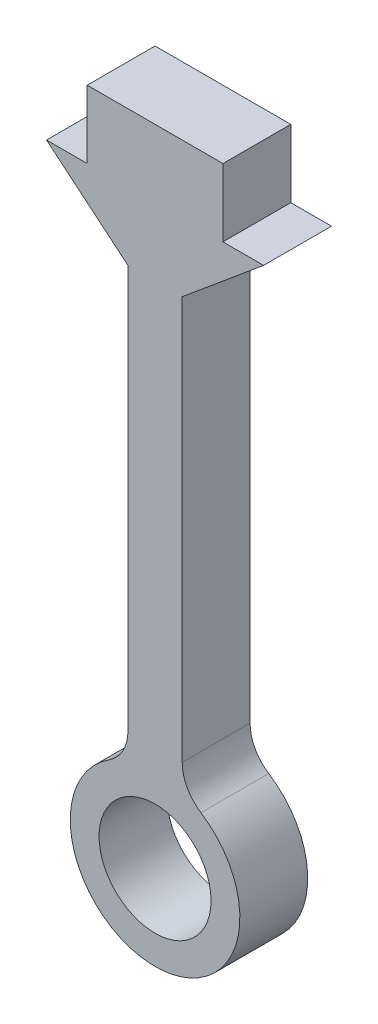
SolidWorks part; units mm, degrees
ref_plane "Plan de face" through (0, 0, 0) normal (0, 0, 1) x (1, 0, 0)
ref_plane "Plan de dessus" through (0, 0, 0) normal (0, 1, 0) x (1, 0, 0)
ref_plane "Plan de droite" through (0, 0, 0) normal (1, 0, 0) x (0, 0, -1)
sketch "Esquisse1" plane through (0, 0, 0) normal (0, 0, 1) x (1, 0, 0)
  line L1 (-2.8016, -1.3723) -> (-0.4016, -3.3723)
  line L2 (-0.4016, -3.3723) -> (1.1984, -3.3723)
  line L3 (1.1984, -3.3723) -> (3.5984, -1.3723)
  line L4 (0.3984, 0.6277) -> (0.3984, -1.3723) construction
  line L5 (-1.6016, -1.3723) -> (2.3984, -1.3723)
  line L6 (-1.6016, -1.3723) -> (-1.6016, 0.6277)
  line L7 (-1.6016, 0.6277) -> (2.3984, 0.6277)
  line L8 (2.3984, -1.3723) -> (2.3984, 0.6277)
  line L9 (-2.8016, -1.3723) -> (-1.6016, -1.3723)
  line L10 (-0.4016, -3.3723) -> (1.1984, -3.3723)
  line L11 (-0.4016, -3.3723) -> (-0.4016, -18.3723)
  line L12 (-0.4016, -18.3723) -> (1.1984, -18.3723)
  line L13 (1.1984, -3.3723) -> (1.1984, -18.3723)
  line L14 (2.3984, -1.3723) -> (3.5984, -1.3723)
  circle A0 centre (0.3984, -18.3723) radius 2.5
  circle A1 centre (0.3984, -18.3723) radius 1.65
  point P15 (0, 0)
  dimension "D7" = 3.3
  dimension "D8" = 5
  dimension "D1" = 2
  dimension "D2" = 1.6
  dimension "D3" = 1.2
  dimension "D4" = 4
  dimension "D5" = 2
  dimension "D6" = 15
extrude "Boss.-Extru.1" add sketch "Esquisse1" along normal blind 2 contours A0 L13 L2 L11 | L2 L3 L5 L1 | L7 L4 L5 L8 | L4 L7 L6 | A1 L13 A0 L11 | A1 L11 A0 L13 region at (0.3984, -2.1723, 0) region at (0.3984, -9.644, 0) region at (-0.6016, -0.3723, 0) region at (0.3984, -16.3538, 0) region at (-0.4714, -16.4664, 0) region at (1.3984, -0.3723, 0)
fillet "Congé1" radius 1.2 2 edges at (-0.4016, -16.0037, 1) (1.1984, -16.0037, 1)
